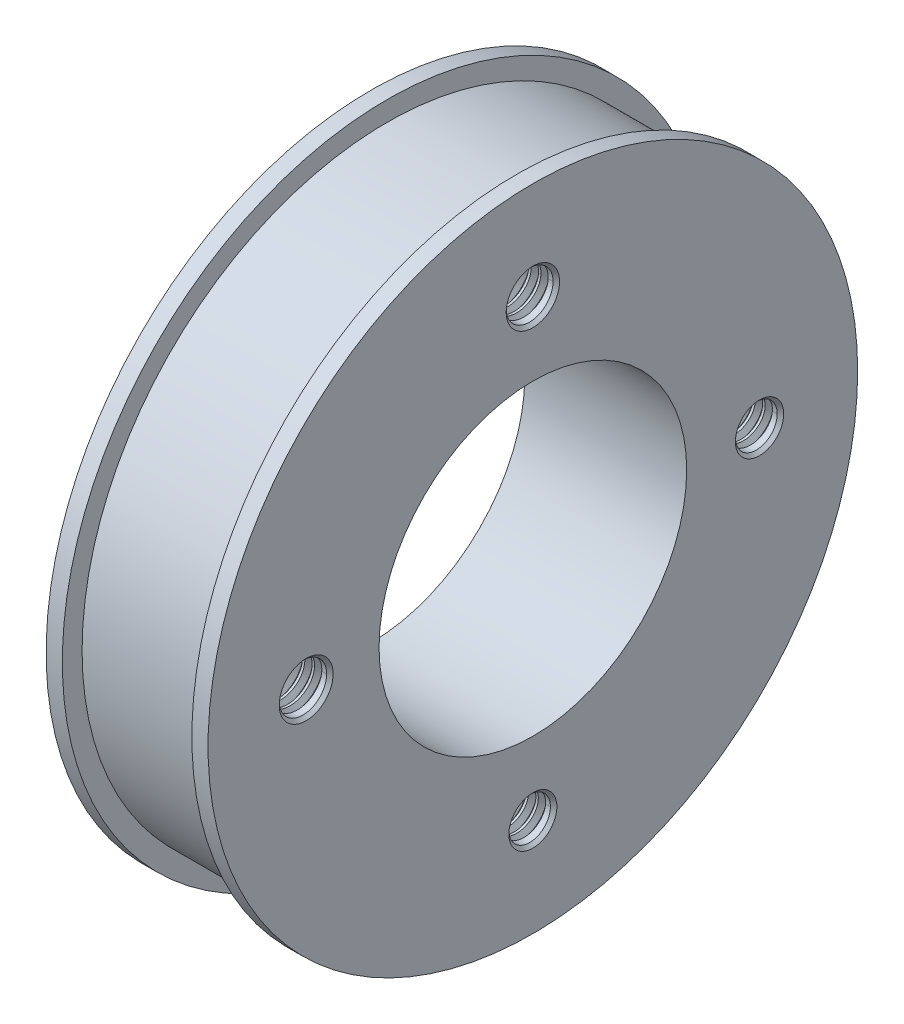
SolidWorks part; units mm, degrees
material "6061 Alloy"
ref_plane "Front Plane" through (0, 0, 0) normal (1, 0, 0) x (0, 1, 0)
ref_plane "Top Plane" through (0, 0, 0) normal (0, 0, 1) x (0, 1, 0)
ref_plane "Right Plane" through (0, 0, 0) normal (0, 1, 0) x (-1, 0, 0)
sketch "Sketch2" plane through (0, 0, 0) normal (1, 0, 0) x (0, 1, 0)
  circle A0 centre (0, 0) radius 20.06
  dimension "D1" = 40.12
extrude "Boss-Extrude1" add sketch "Sketch2" along normal blind 1
sketch "Sketch3" plane through (1, 0, 0) normal (1, 0, 0) x (0, 1, 0)
  circle A0 centre (0, 0) radius 18.84
  dimension "D1" = 37.68
extrude "Boss-Extrude2" add sketch "Sketch3" along normal blind 8
sketch "Sketch4" plane through (9, 0, 0) normal (1, 0, 0) x (0, 1, 0)
  circle A0 centre (0, 0) radius 20.06
  dimension "D1" = 40.12
extrude "Boss-Extrude4" add sketch "Sketch4" along normal blind 1
sketch "Sketch5" plane through (10, 0, 0) normal (1, 0, 0) x (0, 1, 0)
  circle A0 centre (0, 0) radius 9.5
  circle A1 centre (0, 14) radius 1.4643
  circle A2 centre (0, -14) radius 1.291
  circle A3 centre (14, 0) radius 1.4471
  circle A4 centre (-14, 0) radius 1.2829
  dimension "D1" = 19
  dimension "D2" = 28
  dimension "D3" = 14
  dimension "D4" = 14
  dimension "D5" = 28
extrude "Cut-Extrude1" cut sketch "Sketch5" against normal up to surface (10 mm away) up to face at (0, 0, -20.06)
chamfer "Chamfer1" distance 0.2 angle 45 8 edges at (0, 0, 12.5357) (0, 14, -1.4471) (0, 0, -15.291) (0, -14, -1.2829) (10, 0, -15.291) (10, 14, -1.4471) (10, -14, -1.2829) (10, 0, 12.5357)
thread "Thread4" pitch 0.6 method cut profile "Thread Profile4" start angle 0, offset 0, length 9, pitch 0.6, diameter 2.9286
ref_plane "Plane4" through (9.8, 0, 15.4643) normal (0, -1, 0) x (0, 0, 1)
sketch "Thread Profile4" plane through (9.8, 0, 15.4643) normal (0, -1, 0) x (0, 0, 1)
  line L0 (0, 0) -> (0, 0.6) construction
  line L1 (0, 0) -> (0.3248, 0.1875)
  line L2 (0.3248, 0.1875) -> (0.3248, 0.2625)
  line L3 (0.3248, 0.2625) -> (0, 0.45)
  line L4 (0.3248, 0.225) -> (0, 0.225) construction
  line L11 (0, 0) -> (0, 0.45)
  point P2 (0, 0)
  dimension "Pitch" = 0.6
  dimension "Profile_Angle" = 60
  dimension "Profile_Land" = 0.075
  dimension "Profile_Height" = 0.3248
thread "Thread5" pitch 0.6 method cut profile "Thread Profile5" start angle 0, offset 0, length 9, pitch 0.6, diameter 2.5658
ref_plane "Plane5" through (9.8, -14, 1.2829) normal (0, -1, 0) x (0, 0, 1)
sketch "Thread Profile5" plane through (9.8, -14, 1.2829) normal (0, -1, 0) x (0, 0, 1)
  line L0 (0, 0) -> (0, 0.6) construction
  line L1 (0, 0) -> (0.3248, 0.1875)
  line L2 (0.3248, 0.1875) -> (0.3248, 0.2625)
  line L3 (0.3248, 0.2625) -> (0, 0.45)
  line L4 (0.3248, 0.225) -> (0, 0.225) construction
  line L11 (0, 0) -> (0, 0.45)
  point P2 (0, 0)
  dimension "Pitch" = 0.6
  dimension "Profile_Angle" = 60
  dimension "Profile_Land" = 0.075
  dimension "Profile_Height" = 0.3248
thread "Thread6" pitch 0.6 method cut profile "Thread Profile6" start angle 0, offset 0, length 9, pitch 0.6, diameter 2.8942
ref_plane "Plane6" through (9.8, 14, 1.4471) normal (0, -1, 0) x (0, 0, 1)
sketch "Thread Profile6" plane through (9.8, 14, 1.4471) normal (0, -1, 0) x (0, 0, 1)
  line L0 (0, 0) -> (0, 0.6) construction
  line L1 (0, 0) -> (0.3248, 0.1875)
  line L2 (0.3248, 0.1875) -> (0.3248, 0.2625)
  line L3 (0.3248, 0.2625) -> (0, 0.45)
  line L4 (0.3248, 0.225) -> (0, 0.225) construction
  line L11 (0, 0) -> (0, 0.45)
  point P2 (0, 0)
  dimension "Pitch" = 0.6
  dimension "Profile_Angle" = 60
  dimension "Profile_Land" = 0.075
  dimension "Profile_Height" = 0.3248
thread "Thread7" pitch 0.6 method cut profile "Thread Profile7" start angle 0, offset 0, length 9, pitch 0.6, diameter 2.582
ref_plane "Plane7" through (9.8, 0, -12.709) normal (0, -1, 0) x (0, 0, 1)
sketch "Thread Profile7" plane through (9.8, 0, -12.709) normal (0, -1, 0) x (0, 0, 1)
  line L0 (0, 0) -> (0, 0.6) construction
  line L1 (0, 0) -> (0.3248, 0.1875)
  line L2 (0.3248, 0.1875) -> (0.3248, 0.2625)
  line L3 (0.3248, 0.2625) -> (0, 0.45)
  line L4 (0.3248, 0.225) -> (0, 0.225) construction
  line L11 (0, 0) -> (0, 0.45)
  point P2 (0, 0)
  dimension "Pitch" = 0.6
  dimension "Profile_Angle" = 60
  dimension "Profile_Land" = 0.075
  dimension "Profile_Height" = 0.3248
